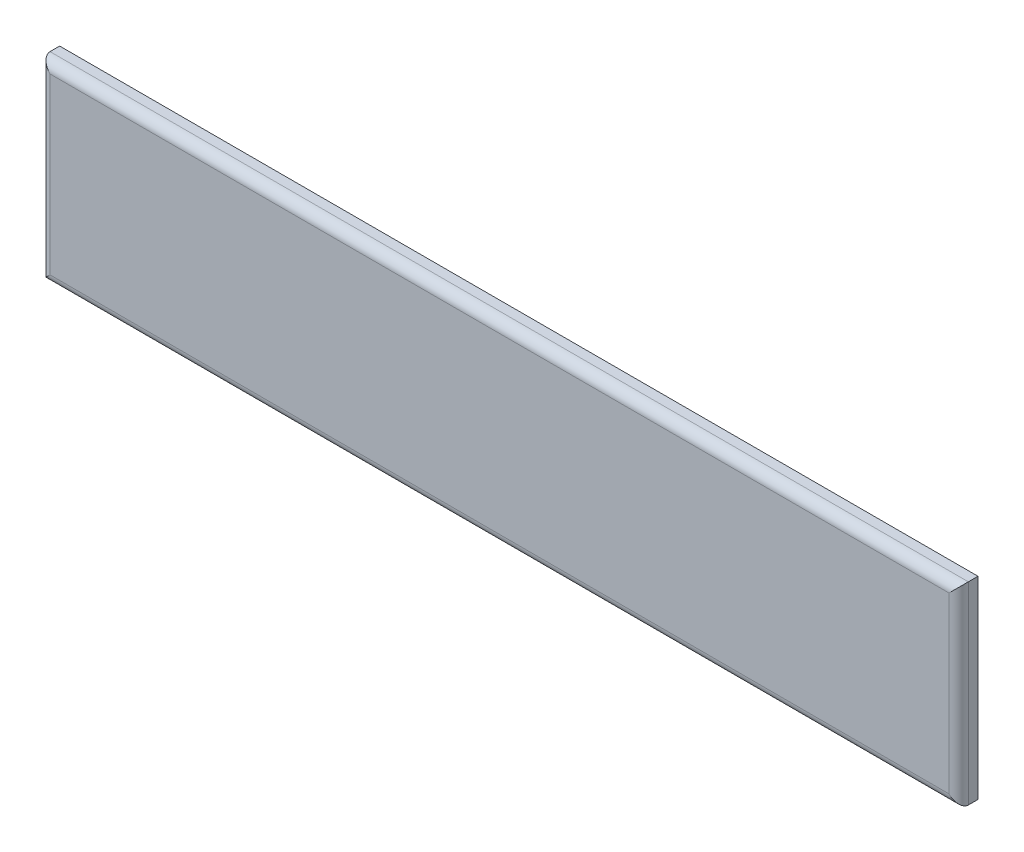
SolidWorks part; units mm, degrees
ref_plane "Front Plane" through (0, 0, 0) normal (0, 0, 1) x (1, 0, 0)
ref_plane "Top Plane" through (0, 0, 0) normal (0, 1, 0) x (1, 0, 0)
ref_plane "Right Plane" through (0, 0, 0) normal (1, 0, 0) x (0, 0, -1)
sketch "Sketch1" plane through (0, 0, 0) normal (0, 0, 1) x (1, 0, 0)
  line L1 (47.5, -10) -> (-47.5, -10)
  line L2 (47.5, -10) -> (47.5, 10)
  line L3 (47.5, 10) -> (-47.5, 10)
  line L4 (-47.5, -10) -> (-47.5, 10)
  line L5 (47.5, -10) -> (-47.5, 10) construction
  line L6 (47.5, 10) -> (-47.5, -10) construction
  point P0 (0, 0)
  dimension "D1" = 95
  dimension "D2" = 20
extrude "Boss-Extrude1" add sketch "Sketch1" along normal mid plane 2
fillet "Fillet1" radius 1 4 edges at (-47.5, 0, 1) (0, -10, 1) (47.5, 0, 1) (0, 10, 1)
hole_wizard "Ø1.0mm Dowel Hole1" positions "Sketch2" profile "Sketch3" hole size "Ø1.0" standard "ANSI Metric"
sketch "Sketch2" plane through (0, 0, -1) normal (0, 0, -1) x (-1, 0, 0)
  line L0 (47.5, -10) -> (-47.5, -10) construction
  line L1 (47.5, 10) -> (47.5, -10) construction
  line L2 (-47.5, -10) -> (-47.5, 10) construction
  point P0 (-44, -8)
  point P2 (-40, -8)
  point P4 (40, -8)
  point P6 (44, -8)
  dimension "D1" = 4
  dimension "D2" = 4
  dimension "D3" = 2
  dimension "D4" = 80
  dimension "D5" = 3.5
  dimension "D6" = 3.5
  dimension "D7" = 2
sketch "Sketch3" plane through (44, -8, -1) normal (1, 0, 0) x (0, 1, 0)
  line L0 (0, 0) -> (0, 1.1502)
  line L1 (0, 1.1502) -> (0.25, 1)
  line L2 (0.25, 1) -> (0.25, 0)
  line L5 (0.25, 0) -> (0, 0)
  line L10 (0, 1.1502) -> (-0.25, 1) construction
  line L11 (0, -6.35) -> (0, 107.95) construction
  dimension "Hole Dia." = 0.5
  dimension "Hole Depth" = 1
  dimension "Drill Angle" = 118
mirror "Mirror1" about plane through (0, 0, 0) normal (0, 1, 0) of "Ø1.0mm Dowel Hole1"
hole_wizard "Ø1.0mm Dowel Hole2" positions "Sketch4" profile "Sketch5" hole size "Ø1.0" standard "ANSI Metric"
sketch "Sketch4" plane through (0, 0, -1) normal (0, 0, -1) x (-1, 0, 0)
  line L0 (-47.5, -10) -> (-47.5, 10) construction
  point P0 (-46.8, 0)
  point P2 (-43.4, 0)
  dimension "D1" = 3.4
  dimension "D2" = 0.7
sketch "Sketch5" plane through (46.8, 0, -1) normal (1, 0, 0) x (0, 1, 0)
  line L0 (0, 0) -> (0, 1.1502)
  line L1 (0, 1.1502) -> (0.25, 1)
  line L2 (0.25, 1) -> (0.25, 0)
  line L5 (0.25, 0) -> (0, 0)
  line L10 (0, 1.1502) -> (-0.25, 1) construction
  line L11 (0, -6.35) -> (0, 107.95) construction
  dimension "Hole Dia." = 0.5
  dimension "Hole Depth" = 1
  dimension "Drill Angle" = 118
mirror "Mirror2" about plane through (0, 0, 0) normal (1, 0, 0) of "Ø1.0mm Dowel Hole2"
ref_plane "Plane1" through (0, 0, 0) normal (0, 0, 1) x (1, 0, 0)
sketch "Sketch6" plane through (0, 0, 0) normal (0, 0, 1) x (1, 0, 0)
  point P0 (0, 0)
